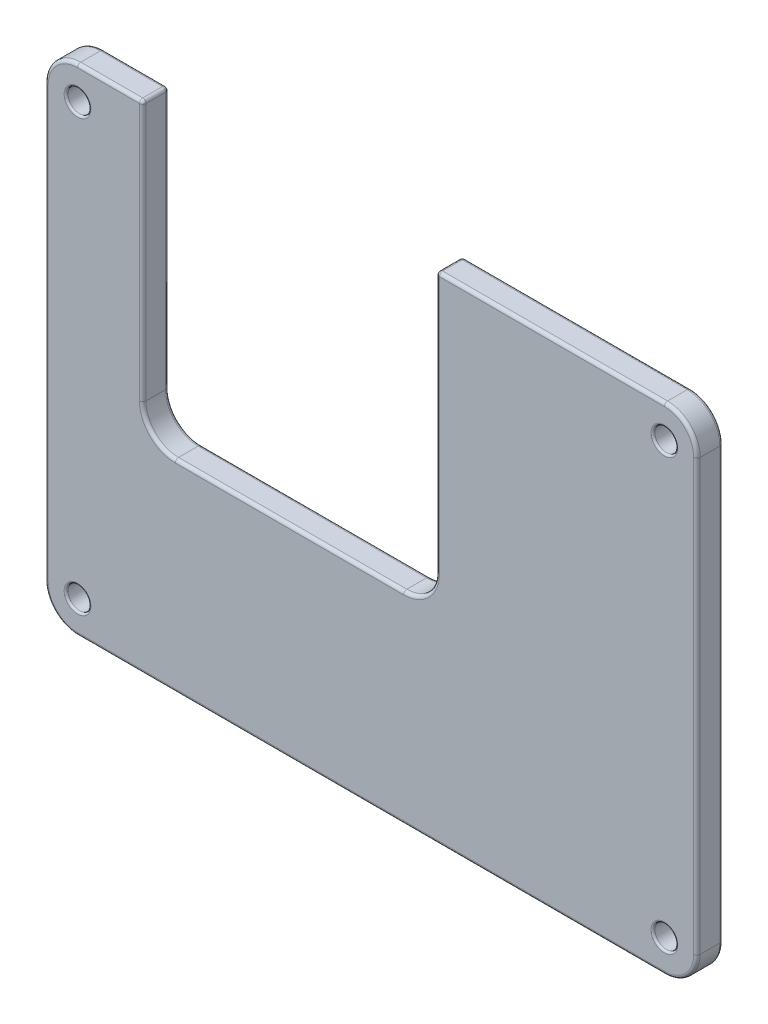
SolidWorks part; units mm, degrees
ref_plane "Front Plane" through (0, 0, 0) normal (0, 0, 1) x (1, 0, 0)
ref_plane "Top Plane" through (0, 0, 0) normal (0, 1, 0) x (1, 0, 0)
ref_plane "Right Plane" through (0, 0, 0) normal (1, 0, 0) x (0, 0, -1)
sketch "Sketch2" plane through (0, 0, 0) normal (0, 0, 1) x (1, 0, 0)
  line L10 (-260, -1421) -> (-270, -1421)
  line L12 (-215, -1421) -> (-215, -1461)
  line L13 (-220, -1466) -> (-255, -1466)
  line L14 (-260, -1421) -> (-260, -1461)
  line L20 (-180, -1421) -> (-215, -1421)
  line L27 (-275, -1426) -> (-275, -1492)
  line L28 (-270, -1497) -> (-180, -1497)
  line L29 (-175, -1492) -> (-175, -1426)
  circle A8 centre (-180, -1492) radius 1.75
  circle A9 centre (-270, -1492) radius 1.75
  circle A10 centre (-270, -1426) radius 1.75
  circle A11 centre (-180, -1426) radius 1.75
  arc A12 (-255, -1466) -> (-260, -1461) centre (-255, -1461) cw
  arc A13 (-215, -1461) -> (-220, -1466) centre (-220, -1461) cw
  arc A16 (-175, -1426) -> (-180, -1421) centre (-180, -1426) ccw
  arc A17 (-270, -1421) -> (-275, -1426) centre (-270, -1426) ccw
  arc A22 (-275, -1492) -> (-270, -1497) centre (-270, -1492) ccw
  arc A23 (-180, -1497) -> (-175, -1492) centre (-180, -1492) ccw
  point P16 (-260, -1466)
  point P21 (-215, -1466)
  dimension "D1" = 3.5
  dimension "D2" = 3.5
  dimension "D3" = 3.5
  dimension "D4" = 3.5
  dimension "D8" = 5
  dimension "D5" = 45
  dimension "D6" = 40
  dimension "D7" = 45
extrude "Boss-Extrude1" add sketch "Sketch2" along normal blind 4
fillet "Fillet1" radius 0.5 19 edges at (-265, -1421, 4) (-273.5355, -1422.4645, 4) (-275, -1459, 4) (-273.5355, -1495.5355, 4) (-225, -1497, 4) (-176.4645, -1495.5355, 4) (-175, -1459, 4) (-176.4645, -1422.4645, 4) (-265, -1421, 0) (-273.5355, -1422.4645, 0) (-275, -1459, 0) (-273.5355, -1495.5355, 0) (-225, -1497, 0) (-176.4645, -1495.5355, 0) (-175, -1459, 0) (-176.4645, -1422.4645, 0) (-197.5, -1421, 4) (-215, -1421, 2) (-197.5, -1421, 0)
fillet "Fillet2" radius 0.5 15 edges at (-214.8536, -1421.1464, 3.8536) (-214.8536, -1421.1464, 0.1464) (-216.4645, -1464.5355, 0) (-237.5, -1466, 0) (-258.5355, -1464.5355, 0) (-260, -1441.25, 0) (-260, -1421.1464, 0.1464) (-260, -1421, 2) (-260, -1421.1464, 3.8536) (-260, -1441.25, 4) (-258.5355, -1464.5355, 4) (-237.5, -1466, 4) (-216.4645, -1464.5355, 4) (-215, -1441.25, 0) (-215, -1441.25, 4)
fillet "Fillet3" radius 0.3 8 edges at (-268.25, -1492, 0) (-268.25, -1492, 4) (-178.25, -1492, 0) (-178.25, -1492, 4) (-178.25, -1426, 0) (-178.25, -1426, 4) (-268.25, -1426, 0) (-268.25, -1426, 4)
